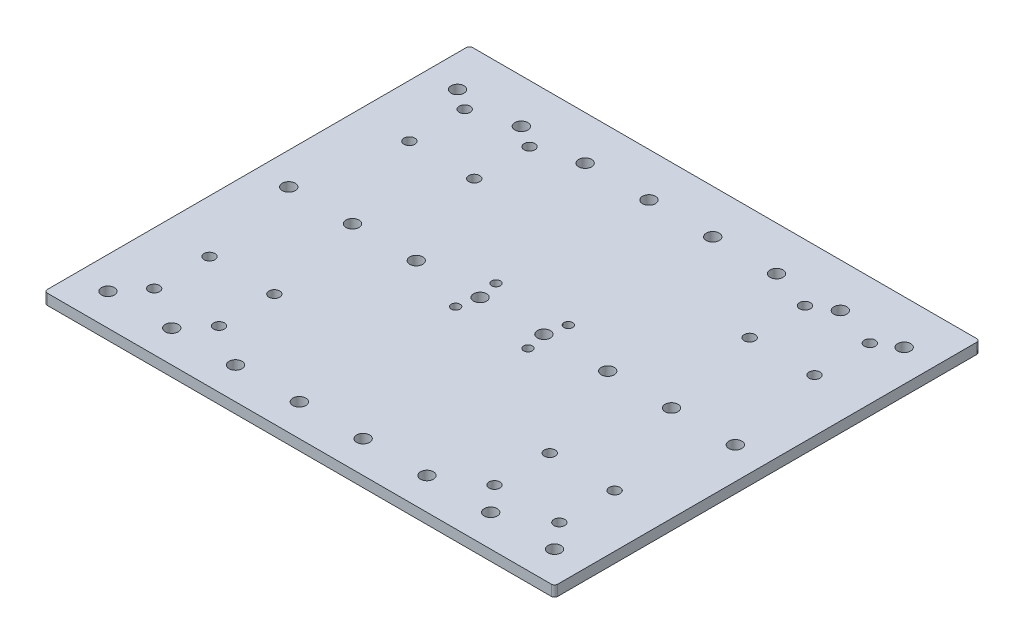
SolidWorks part; units mm, degrees
ref_plane "Front Plane" through (0, 0, 0) normal (0, 0, 1) x (1, 0, 0)
ref_plane "Top Plane" through (0, 0, 0) normal (0, 1, 0) x (1, 0, 0)
ref_plane "Right Plane" through (0, 0, 0) normal (1, 0, 0) x (0, 0, -1)
sketch "Sketch1" plane through (0, 0, 0) normal (0, 1, 0) x (1, 0, 0)
  line L1 (-120, -100) -> (120, -100)
  line L2 (-120, -100) -> (-120, 100)
  line L3 (-120, 100) -> (120, 100)
  line L4 (120, -100) -> (120, 100)
  line L5 (-120, -100) -> (120, 100) construction
  line L6 (-120, 100) -> (120, -100) construction
  point P0 (0, 0)
  dimension "D1" = 240
  dimension "D2" = 200
extrude "Boss-Extrude1" add sketch "Sketch1" along normal mid plane 5
sketch "Sketch2" plane through (0, 2.5, 0) normal (0, 1, 0) x (1, 0, 0)
  line L5 (-80, 100) -> (-80, -100)
  line L6 (-80, 100) -> (-80, -100) construction
  line L8 (80, -100) -> (80, 100)
  line L9 (80, -100) -> (80, 100) construction
  line L11 (120, 60) -> (-120, 60)
  line L12 (120, 60) -> (-120, 60) construction
  line L14 (-120, -60) -> (120, -60)
  line L15 (-120, -60) -> (120, -60) construction
  line L16 (-95.25, 73) -> (-64.75, 73) construction
  line L17 (-95.25, 73) -> (-95.25, 47) construction
  line L18 (-95.25, 47) -> (-64.75, 47) construction
  line L19 (-64.75, 73) -> (-64.75, 47) construction
  line L20 (-95.25, 73) -> (-64.75, 47) construction
  line L21 (-95.25, 47) -> (-64.75, 73) construction
  line L22 (64.75, 47) -> (95.25, 47) construction
  line L23 (64.75, 47) -> (64.75, 73) construction
  line L24 (64.75, 73) -> (95.25, 73) construction
  line L25 (95.25, 47) -> (95.25, 73) construction
  line L26 (64.75, 47) -> (95.25, 73) construction
  line L27 (64.75, 73) -> (95.25, 47) construction
  line L28 (64.75, -47) -> (95.25, -47) construction
  line L29 (64.75, -47) -> (64.75, -73) construction
  line L30 (64.75, -73) -> (95.25, -73) construction
  line L31 (95.25, -47) -> (95.25, -73) construction
  line L32 (64.75, -47) -> (95.25, -73) construction
  line L33 (64.75, -73) -> (95.25, -47) construction
  line L34 (-95.25, -73) -> (-64.75, -73) construction
  line L35 (-95.25, -73) -> (-95.25, -47) construction
  line L36 (-95.25, -47) -> (-64.75, -47) construction
  line L37 (-64.75, -73) -> (-64.75, -47) construction
  line L38 (-95.25, -73) -> (-64.75, -47) construction
  line L39 (-95.25, -47) -> (-64.75, -73) construction
  circle A0 centre (-95.25, 73) radius 2.55
  circle A1 centre (-95.25, 47) radius 2.55
  circle A2 centre (-64.75, 73) radius 2.55
  circle A3 centre (-64.75, 47) radius 2.55
  circle A4 centre (-95.25, -47) radius 2.55
  circle A5 centre (-95.25, -73) radius 2.55
  circle A6 centre (-64.75, -73) radius 2.55
  circle A7 centre (-64.75, -47) radius 2.55
  circle A8 centre (95.25, -47) radius 2.55
  circle A9 centre (64.75, -47) radius 2.55
  circle A10 centre (64.75, -73) radius 2.55
  circle A11 centre (95.25, -73) radius 2.55
  circle A12 centre (64.75, 73) radius 2.55
  circle A13 centre (64.75, 47) radius 2.55
  circle A14 centre (95.25, 73) radius 2.55
  circle A15 centre (95.25, 47) radius 2.55
  point P0 (-80, 60)
  point P13 (80, 60)
  point P18 (80, -60)
  point P23 (-80, -60)
  dimension "D13" = 5.1
  dimension "D14" = 5.1
  dimension "D15" = 5.1
  dimension "D16" = 5.1
  dimension "D17" = 5.1
  dimension "D18" = 5.1
  dimension "D19" = 5.1
  dimension "D20" = 5.1
  dimension "D21" = 5.1
  dimension "D22" = 5.1
  dimension "D23" = 5.1
  dimension "D24" = 5.1
  dimension "D25" = 5.1
  dimension "D26" = 5.1
  dimension "D27" = 5.1
  dimension "D28" = 5.1
  dimension "D1" = 40
  dimension "D5" = 30.5
  dimension "D6" = 26
  dimension "D7" = 30.5
  dimension "D8" = 26
  dimension "D9" = 26
  dimension "D10" = 30.5
  dimension "D11" = 26
  dimension "D12" = 30.5
  dimension "D2" = 40
  dimension "D3" = 40
  dimension "D4" = 40
extrude "Cut-Extrude1" cut sketch "Sketch2" against normal through all
sketch "Sketch3" plane through (0, 2.5, 0) normal (0, 1, 0) x (1, 0, 0)
  line L1 (-17, -9.5) -> (17, -9.5) construction
  line L2 (-17, -9.5) -> (-17, 9.5) construction
  line L3 (-17, 9.5) -> (17, 9.5) construction
  line L4 (17, -9.5) -> (17, 9.5) construction
  line L5 (-17, -9.5) -> (17, 9.5) construction
  line L6 (-17, 9.5) -> (17, -9.5) construction
  circle A0 centre (-17, 9.5) radius 2.05
  circle A1 centre (17, 9.5) radius 2.05
  circle A2 centre (17, -9.5) radius 2.05
  circle A3 centre (-17, -9.5) radius 2.05
  point P0 (0, 0)
  dimension "D3" = 4.1
  dimension "D4" = 4.1
  dimension "D5" = 4.1
  dimension "D6" = 4.1
  dimension "D1" = 34
  dimension "D2" = 19
extrude "Cut-Extrude2" cut sketch "Sketch3" against normal through all
sketch "Sketch4" plane through (0, 2.5, 0) normal (0, 1, 0) x (1, 0, 0)
  line L0 (-105, 100) -> (-105, -100) construction
  line L1 (120, 100) -> (-120, 100) construction
  line L2 (-120, -100) -> (120, -100) construction
  line L3 (-120, 100) -> (-120, -100) construction
  line L4 (-75, 100) -> (-75, -100) construction
  line L5 (-45, 100) -> (-45, -100) construction
  line L6 (-15, 100) -> (-15, -100) construction
  line L7 (15, 100) -> (15, -100) construction
  line L8 (45, 100) -> (45, -100) construction
  line L9 (75, 100) -> (75, -100) construction
  line L10 (105, 100) -> (105, -100) construction
  line L11 (-120, -85) -> (120, -85) construction
  line L12 (-120, 100) -> (-120, -100) construction
  line L13 (120, -100) -> (120, 100) construction
  line L14 (-120, 79.3935) -> (120, 79.3935) construction
  line L15 (-120, 0) -> (120, 0) construction
  circle A0 centre (-105, 79.3935) radius 3.05
  circle A1 centre (-75, 79.3935) radius 3.05
  circle A2 centre (-45, 79.3935) radius 3.05
  circle A3 centre (-15, 79.3935) radius 3.05
  circle A4 centre (15, 79.3935) radius 3.05
  circle A5 centre (45, 79.3935) radius 3.05
  circle A6 centre (75, 79.3935) radius 3.05
  circle A7 centre (105, 79.3935) radius 3.05
  circle A8 centre (-105, 0) radius 3.05
  circle A9 centre (-105, -85) radius 3.05
  circle A10 centre (-75, 0) radius 3.05
  circle A11 centre (-45, 0) radius 3.05
  circle A12 centre (-15, 0) radius 3.05
  circle A13 centre (15, 0) radius 3.05
  circle A14 centre (45, 0) radius 3.05
  circle A15 centre (75, 0) radius 3.05
  circle A16 centre (105, 0) radius 3.05
  circle A17 centre (-75, -85) radius 3.05
  circle A18 centre (-45, -85) radius 3.05
  circle A19 centre (-15, -85) radius 3.05
  circle A20 centre (15, -85) radius 3.05
  circle A21 centre (45, -85) radius 3.05
  circle A22 centre (75, -85) radius 3.05
  circle A23 centre (105, -85) radius 3.05
  point P6 (-120, 0)
  dimension "D3" = 6.1
  dimension "D4" = 6.1
  dimension "D5" = 6.1
  dimension "D1" = 15
  dimension "D2" = 15
extrude "Cut-Extrude3" cut sketch "Sketch4" against normal through all
fillet "Fillet1" radius 1.5 4 edges at (-120, 0, -100) (120, 0, -100) (-120, 0, 100) (120, 0, 100)
equation "\"D4@Sketch4\"=\"D3@Sketch4\""
equation "\"D5@Sketch4\"=\"D3@Sketch4\""
